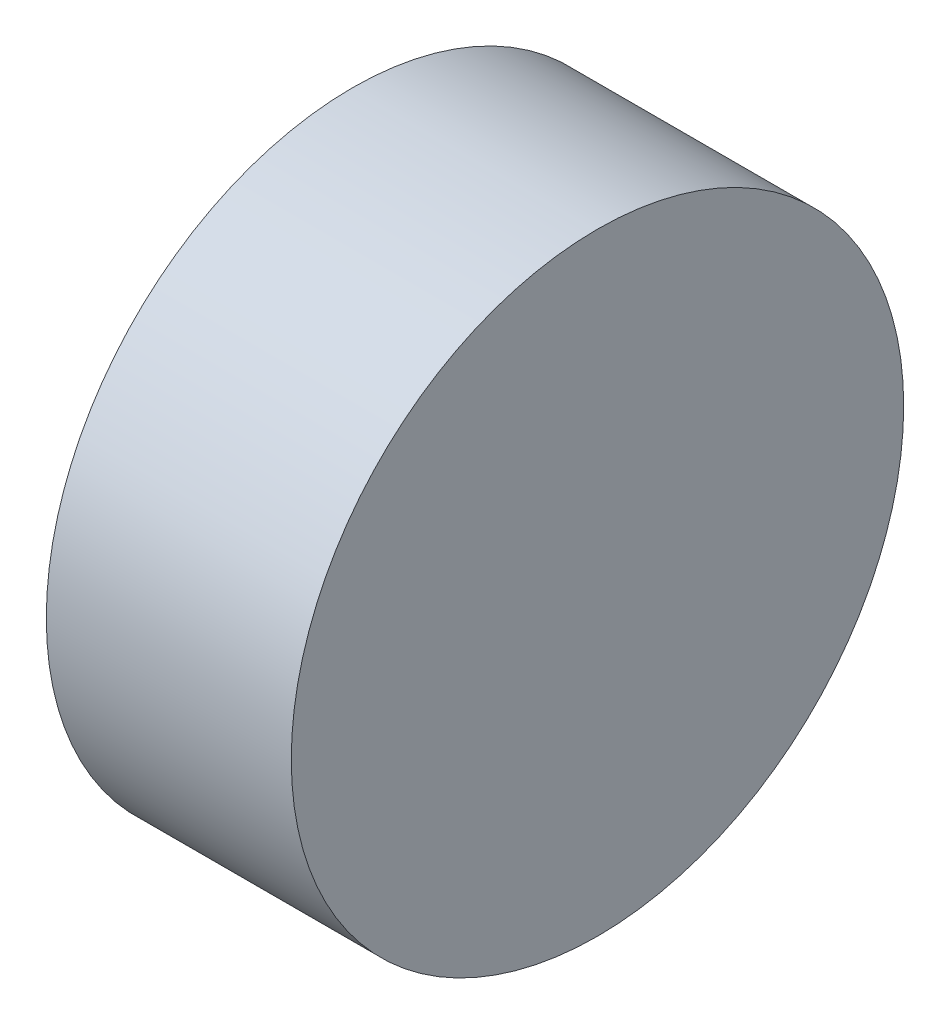
SolidWorks part; units mm, degrees
ref_plane "Front Plane" through (0, 0, 0) normal (0, 0, 1) x (1, 0, 0)
ref_plane "Top Plane" through (0, 0, 0) normal (0, 1, 0) x (1, 0, 0)
ref_plane "Right Plane" through (0, 0, 0) normal (1, 0, 0) x (0, 0, -1)
sketch "Sketch1" plane through (0, 0, 0) normal (1, 0, 0) x (0, 0, -1)
  circle A0 centre (0, -2480) radius 2500
  point P2 (0, 0)
  dimension "D1" = 5000
  dimension "D2" = 2480
extrude "Boss-Extrude1" add sketch "Sketch1" along normal blind 1000 and the other way blind 1000
